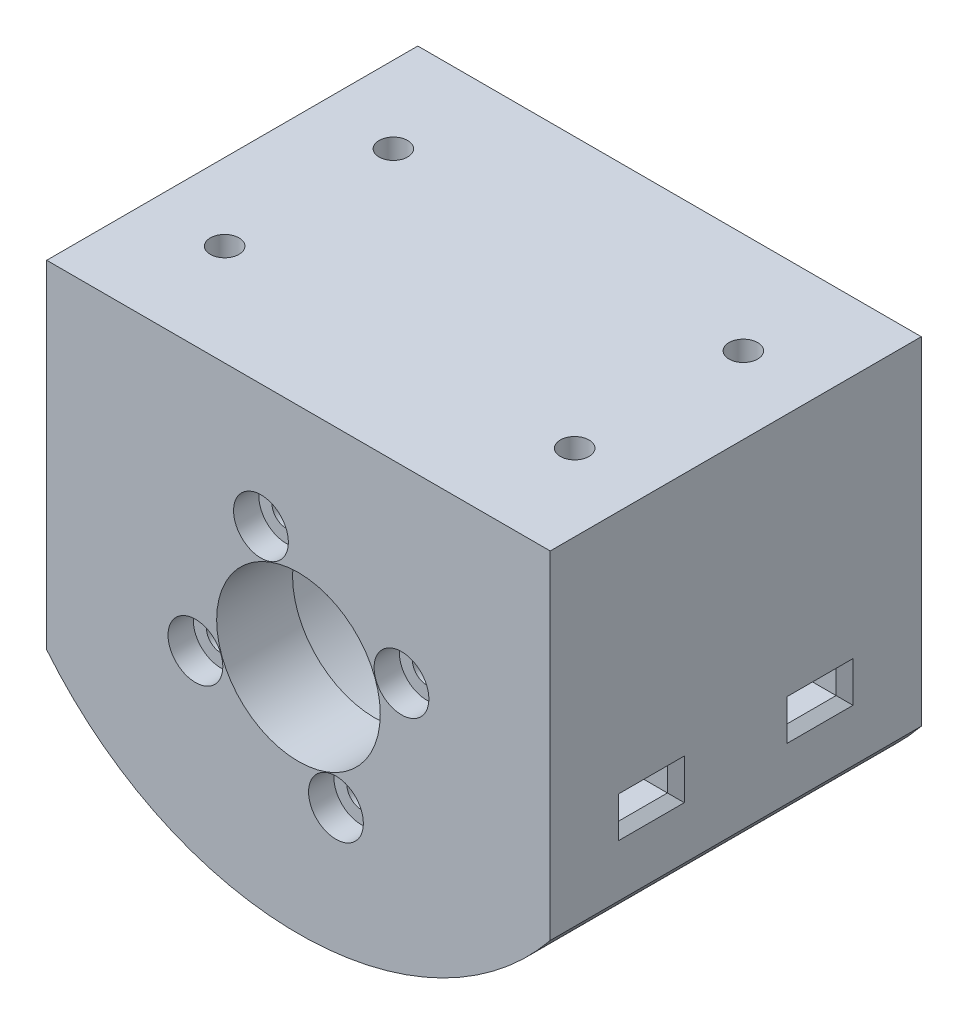
SolidWorks part; units mm, degrees
ref_plane "Front Plane" through (0, 0, 0) normal (0, 0, 1) x (1, 0, 0)
ref_plane "Top Plane" through (0, 0, 0) normal (0, 1, 0) x (1, 0, 0)
ref_plane "Right Plane" through (0, 0, 0) normal (1, 0, 0) x (0, 0, -1)
sketch "Sketch1" plane through (0, 0, 0) normal (0, 0, 1) x (1, 0, 0)
  line L0 (-29.85, 15.8435) -> (29.85, 15.8435)
  line L1 (-29.85, -24.1565) -> (29.85, -24.1565)
  line L2 (-29.85, -24.1565) -> (-29.85, 24.1565)
  line L3 (-29.85, 24.1565) -> (29.85, 24.1565)
  line L4 (29.85, -24.1565) -> (29.85, 24.1565)
  line L5 (-29.85, -24.1565) -> (29.85, 24.1565) construction
  line L6 (-29.85, 24.1565) -> (29.85, -24.1565) construction
  circle A0 centre (0, -11) radius 16.2
  circle A1 centre (0, 0) radius 38.4
  point P0 (0, 0)
  dimension "D2" = 32.4
  dimension "D4" = 76.8
  dimension "D1" = 59.7
  dimension "D3" = 11
  dimension "D5" = 40
extrude "Boss-Extrude1" add sketch "Sketch1" along normal blind 44 contours L1 A1 A0 | A0 L1 L4 L0 L2 | L1 A0 | L1 A0 region at (0, 15.1249, 0) region at (0, -30.2791, 0) region at (0, -10.2831, 0) region at (0, -25.3843, 0)
extrude "Cut-Extrude1" cut sketch "Sketch1<3>" along normal blind 35 contours L1 A0 | L1 A0 region at (0, -10.2831, 0) region at (0, -25.3843, 0)
sketch "Sketch1<3>" plane through (0, 0, 0) normal (0, 0, 1) x (1, 0, 0) same geometry as "Sketch1"
sketch "Sketch2" plane through (0, 0, 44) normal (0, 0, 1) x (1, 0, 0)
  circle A0 centre (0, -11) radius 9.7
  dimension "D1" = 19.4
extrude "Cut-Extrude2" cut sketch "Sketch2" against normal up to next
sketch "Sketch3" plane through (0, 0, 44) normal (0, 0, 1) x (1, 0, 0)
  line L0 (0, -11) -> (0, 2) construction
  line L1 (0, -11) -> (-4.4463, 1.216) construction
  circle A0 centre (0, -11) radius 13 construction
  point P4 (12.216, -6.5537)
  point P5 (4.4463, -23.216)
  point P6 (-4.4463, 1.216)
  point P10 (-12.216, -15.4463)
  dimension "D1" = 26
  dimension "D2" = 20
  dimension "D3" = 4
hole_wizard "CBORE for M3 SHCS1" positions "Sketch3" profile "Sketch4" counterbore size "M3" standard "ANSI Metric" end condition up to next
sketch "Sketch4" plane through (-12.216, -15.4463, 44) normal (1, 0, 0) x (0, -1, 0)
  line L0 (0, 0) -> (0, 9)
  line L1 (0, 9) -> (1.7, 9)
  line L3 (1.7, 9) -> (1.7, 3)
  line L4 (1.7, 3) -> (3.25, 3)
  line L5 (3.25, 3) -> (3.25, 0)
  line L7 (3.25, 0) -> (0, 0)
  line L11 (0, -6.35) -> (0, 107.95) construction
  dimension "Thru Hole Dia." = 3.4
  dimension "Thru Hole Depth" = 9
  dimension "C'Bore Dia." = 6.5
  dimension "C'Bore Depth" = 3
ref_plane "Plane1" through (0, -24.1565, 0) normal (0, 1, 0) x (1, 0, 0)
ref_plane "Plane2" through (0, -44.1565, 0) normal (0, -1, 0) x (-1, 0, 0)
sketch "Sketch6" plane through (0, -44.1565, 0) normal (0, -1, 0) x (-1, 0, 0)
  line L0 (0, 0) -> (0, -44) construction
  line L1 (-38.4, 0) -> (38.4, 0) construction
  line L2 (-29.85, -44) -> (29.85, -44) construction
  line L3 (29.85, -22) -> (-29.85, -22) construction
  line L4 (29.85, -44) -> (29.85, 0) construction
  line L5 (-29.85, -44) -> (-29.85, 0) construction
  circle A0 centre (20.75, -12) radius 1.7
  circle A1 centre (-20.75, -12) radius 1.7
  circle A2 centre (20.75, -32) radius 1.7
  circle A3 centre (-20.75, -32) radius 1.7
  dimension "D1" = 3.4
  dimension "D2" = 12
  dimension "D3" = 41.5
extrude "Cut-Extrude3" cut sketch "Sketch6" against normal up to next
ref_plane "Plane3" through (0, -14.1565, 0) normal (0, 1, 0) x (1, 0, 0)
sketch "Sketch7" plane through (0, -14.1565, 0) normal (0, 1, 0) x (1, 0, 0)
  line L0 (22.4243, -9.1) -> (22.4243, -14.9)
  line L1 (-19.0757, -9.1) -> (-22.4243, -9.1)
  line L2 (-22.4243, -9.1) -> (-24.0986, -12)
  line L3 (-24.0986, -12) -> (-22.4243, -14.9)
  line L4 (-22.4243, -14.9) -> (-19.0757, -14.9)
  line L5 (-19.0757, -14.9) -> (-17.4014, -12)
  line L6 (-17.4014, -12) -> (-19.0757, -9.1)
  line L8 (22.4243, -9.1) -> (29.85, -9.1)
  line L9 (22.4243, -14.9) -> (29.85, -14.9)
  line L10 (29.85, -9.1) -> (29.85, -14.9)
  line L11 (17.4014, -12) -> (19.0757, -14.9)
  line L12 (19.0757, -14.9) -> (22.4243, -14.9)
  line L13 (22.4243, -14.9) -> (24.0986, -12)
  line L14 (24.0986, -12) -> (22.4243, -9.1)
  line L15 (22.4243, -9.1) -> (19.0757, -9.1)
  line L16 (19.0757, -9.1) -> (17.4014, -12)
  line L17 (-22.4243, -29.1) -> (-24.0986, -32)
  line L18 (-24.0986, -32) -> (-22.4243, -34.9)
  line L19 (-22.4243, -34.9) -> (-19.0757, -34.9)
  line L20 (-19.0757, -34.9) -> (-17.4014, -32)
  line L21 (-17.4014, -32) -> (-19.0757, -29.1)
  line L22 (-19.0757, -29.1) -> (-22.4243, -29.1)
  line L23 (22.4243, -29.1) -> (19.0757, -29.1)
  line L24 (19.0757, -29.1) -> (17.4014, -32)
  line L25 (17.4014, -32) -> (19.0757, -34.9)
  line L26 (19.0757, -34.9) -> (22.4243, -34.9)
  line L27 (22.4243, -34.9) -> (24.0986, -32)
  line L28 (24.0986, -32) -> (22.4243, -29.1)
  line L30 (22.4243, -29.1) -> (22.4243, -34.9)
  line L32 (22.4243, -29.1) -> (29.85, -29.1)
  line L33 (22.4243, -34.9) -> (29.85, -34.9)
  line L34 (29.85, -29.1) -> (29.85, -34.9)
  line L35 (-22.4243, -34.9) -> (-22.4243, -29.1)
  line L36 (-22.4243, -34.9) -> (-29.85, -34.9)
  line L37 (-22.4243, -29.1) -> (-29.85, -29.1)
  line L38 (-29.85, -34.9) -> (-29.85, -29.1)
  line L39 (-22.4243, -14.9) -> (-22.4243, -9.1)
  line L40 (-22.4243, -14.9) -> (-29.85, -14.9)
  line L41 (-22.4243, -9.1) -> (-29.85, -9.1)
  line L42 (-29.85, -14.9) -> (-29.85, -9.1)
  line L45 (-29.85, -44) -> (-29.85, 0) construction
  line L46 (29.85, -44) -> (29.85, 0) construction
  circle A0 centre (-20.75, -12) radius 2.9 construction
  circle A1 centre (20.75, -12) radius 2.9 construction
  circle A2 centre (-20.75, -32) radius 2.9 construction
  circle A3 centre (20.75, -32) radius 2.9 construction
  point P48 (28.6337, -9.1)
  dimension "D1" = 5.8
extrude "Cut-Extrude4" cut sketch "Sketch7" against normal blind 2.8 contours L42 L40 L3 L2 L41 | L3 L39 L2 | L39 L4 L5 L6 L1 | L38 L36 L18 L17 L37 | L18 L35 L17 | L35 L19 L20 L21 L22 | L30 L23 L24 L25 L26 | L34 L32 L28 L27 L33 | L28 L30 L27 | L14 L13 L9 L10 L8 | L13 L14 L0 | L15 L16 L11 L12 L0 region at (22.9824, -14.1565, 12) region at (26.538, -14.1565, 12) region at (20.3035, -14.1565, 12) region at (-20.3035, -14.1565, 12) region at (-22.9824, -14.1565, 12) region at (-26.538, -14.1565, 12) region at (-22.9824, -14.1565, 32) region at (-20.3035, -14.1565, 32) region at (-26.538, -14.1565, 32) region at (20.3035, -14.1565, 32) region at (26.538, -14.1565, 32) region at (22.9824, -14.1565, 32)
chamfer "Chamfer1" distance 1 angle 45 16 edges at (-29.85, -14.1565, 32) (-29.85, -15.5565, 29.1) (-29.85, -16.9565, 32) (-29.85, -15.5565, 34.9) (-29.85, -14.1565, 12) (-29.85, -15.5565, 9.1) (-29.85, -16.9565, 12) (-29.85, -15.5565, 14.9) (29.85, -15.5565, 29.1) (29.85, -14.1565, 32) (29.85, -15.5565, 34.9) (29.85, -16.9565, 32) (29.85, -15.5565, 9.1) (29.85, -14.1565, 12) (29.85, -15.5565, 14.9) (29.85, -16.9565, 12)
